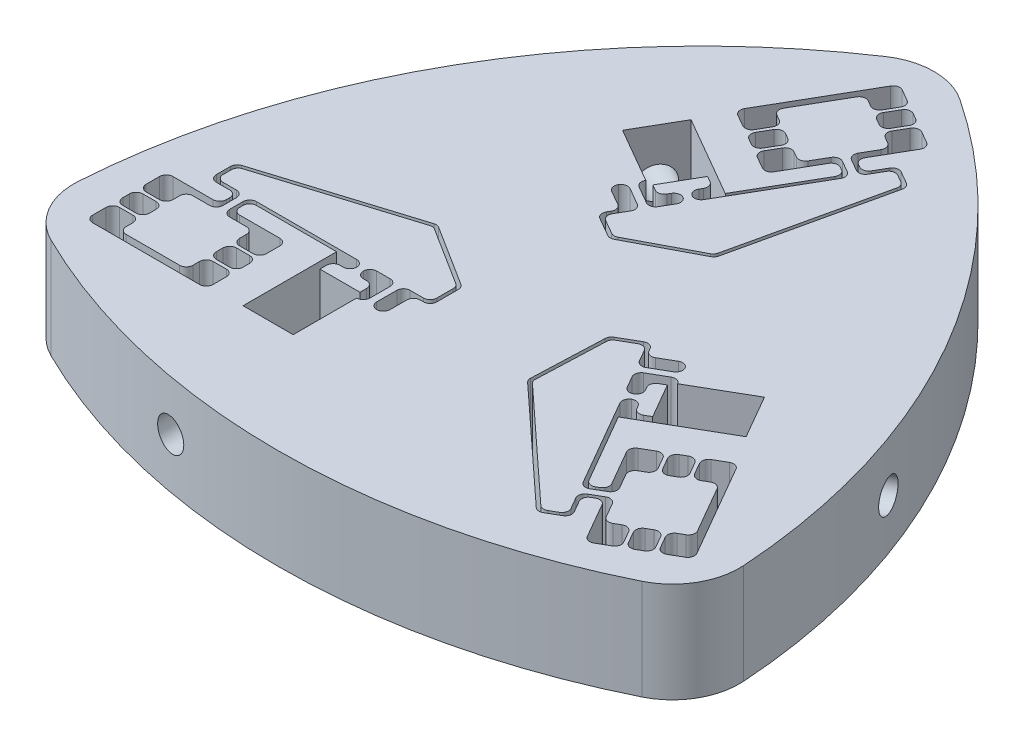
SolidWorks part; units mm, degrees
material "7050-T73510"
ref_plane "Front Plane" through (0, 0, 0) normal (0, 0, 1) x (1, 0, 0)
ref_plane "Top Plane" through (0, 0, 0) normal (0, 1, 0) x (1, 0, 0)
ref_plane "Right Plane" through (0, 0, 0) normal (1, 0, 0) x (0, 0, -1)
sketch "Bass" plane through (0, 0, 0) normal (0, 1, 0) x (1, 0, 0)
  line L1 (0, 57.735) -> (-50, -28.8675) construction
  line L2 (-50, -28.8675) -> (50, -28.8675) construction
  line L3 (50, -28.8675) -> (0, 57.735) construction
  circle A0 centre (0, 0) radius 28.8675 construction
  arc A1 (0, 57.735) -> (50, -28.8675) centre (-50, -28.8675) cw
  arc A2 (-50, -28.8675) -> (0, 57.735) centre (50, -28.8675) cw
  arc A3 (-50, -28.8675) -> (50, -28.8675) centre (0, 57.735) ccw
  dimension "D1" = 100
extrude "Drop the" add sketch "Bass" against normal blind 15
sketch "Flexin" plane through (0, 0, 0) normal (0, -1, 0) x (1, 0, 0)
  line L0 (-8.4558, -18.5533) -> (-7.9558, -19.4193)
  line L1 (-7.9558, -19.4193) -> (-3.6256, -16.9193)
  line L2 (-3.6256, -16.9193) -> (-1.6256, -20.3834)
  line L5 (-1.6256, -20.3834) -> (-3.3577, -21.3834)
  line L6 (-3.3577, -21.3834) -> (-4.6077, -19.2184)
  line L7 (-4.6077, -19.2184) -> (-6.3397, -20.2184)
  line L8 (-6.3397, -20.2184) -> (-3.3397, -25.4145)
  line L9 (-3.3397, -25.4145) -> (-1.6077, -24.4145)
  line L10 (-1.6077, -24.4145) -> (-2.8577, -22.2495)
  line L11 (-2.8577, -22.2495) -> (-1.1256, -21.2495)
  line L14 (-1.1256, -21.2495) -> (7.3744, -35.9719)
  line L15 (7.3744, -35.9719) -> (3.9103, -37.9719)
  line L16 (3.9103, -37.9719) -> (1.6603, -34.0748)
  line L17 (1.6603, -34.0748) -> (-0.9378, -35.5748)
  line L18 (-0.9378, -35.5748) -> (-2.9378, -32.1107)
  line L19 (-2.9378, -32.1107) -> (-3.3708, -32.3607)
  line L20 (-3.3708, -32.3607) -> (-1.3708, -35.8248)
  line L21 (-1.3708, -35.8248) -> (-3.9689, -37.3248)
  line L22 (-3.9689, -37.3248) -> (-5.9689, -33.8607)
  line L23 (-5.9689, -33.8607) -> (-6.4019, -34.1107)
  line L24 (-6.4019, -34.1107) -> (-4.4019, -37.5748)
  line L25 (-4.4019, -37.5748) -> (-7, -39.0748)
  line L26 (-7, -39.0748) -> (-2, -47.735)
  line L27 (-2, -47.735) -> (0.5981, -46.235)
  line L28 (0.5981, -46.235) -> (2.5981, -49.6991)
  line L29 (2.5981, -49.6991) -> (3.0311, -49.4491)
  line L30 (3.0311, -49.4491) -> (1.0311, -45.985)
  line L31 (1.0311, -45.985) -> (3.6292, -44.485)
  line L32 (3.6292, -44.485) -> (5.6292, -47.9491)
  line L33 (5.6292, -47.9491) -> (6.0622, -47.6991)
  line L34 (6.0622, -47.6991) -> (4.0622, -44.235)
  line L35 (4.0622, -44.235) -> (6.6603, -42.735)
  line L36 (6.6603, -42.735) -> (4.4103, -38.8379)
  line L37 (4.4103, -38.8379) -> (7.8744, -36.8379)
  line L38 (7.8744, -36.8379) -> (9.8744, -40.302)
  line L39 (9.8744, -40.302) -> (12.4724, -38.802)
  line L40 (12.4724, -38.802) -> (7.2846, -15.8164)
  line L41 (7.2846, -15.8164) -> (-2.6615, -10.5892)
  line L42 (-2.6615, -10.5892) -> (-6.1256, -12.5892)
  line L43 (-6.1256, -12.5892) -> (-4.1256, -16.0533)
  line L44 (-4.1256, -16.0533) -> (-8.4558, -18.5533)
  line L45 (-8.2058, -18.9863) -> (-3.8756, -16.4863) construction
  line L46 (-4.8397, -22.8164) -> (-1.3756, -20.8164) construction
  line L47 (-4.5, -43.4049) -> (7.6244, -36.4049) construction
  line L48 (-15.683, -25.0354) -> (-7.4558, -20.2854)
  line L49 (-7.4558, -20.2854) -> (-7.9558, -19.4193)
  line L50 (-9.866, -36.1107) -> (-0.866, -51.6991)
  line L51 (-0.866, -51.6991) -> (2.5981, -49.6991)
  line L52 (3.0311, -49.4491) -> (5.6292, -47.9491)
  line L53 (-15.683, -25.0354) -> (-11.933, -31.5305)
  line L54 (-11.933, -31.5305) -> (0.1913, -24.5305)
  line L55 (6.0622, -47.6991) -> (9.5263, -45.6991)
  line L56 (-9.866, -36.1107) -> (-6.4019, -34.1107)
  line L57 (0.1913, -24.5305) -> (6.6913, -35.7889)
  line L58 (6.6913, -35.7889) -> (4.5263, -37.0389)
  line L59 (4.5263, -37.0389) -> (0.5263, -30.1107)
  line L64 (-5.9689, -33.8607) -> (-3.3708, -32.3607)
  line L65 (-2.9378, -32.1107) -> (0.5263, -30.1107)
  line L66 (9.5263, -45.6991) -> (5.5263, -38.7709)
  line L78 (5.5263, -38.7709) -> (7.6913, -37.5209)
  line L79 (7.6913, -37.5209) -> (9.6913, -40.985)
  line L80 (9.6913, -40.985) -> (13.0412, -39.051)
  line L81 (13.0412, -39.051) -> (7.7215, -15.4812)
  line L82 (7.7215, -15.4812) -> (-2.6729, -10.0184)
  line L83 (-2.6729, -10.0184) -> (-6.8087, -12.4062)
  line L84 (-6.8087, -12.4062) -> (-5.5587, -14.5713)
  line L85 (-5.5587, -14.5713) -> (-9.4558, -16.8213)
  line L88 (-8.4558, -18.5533) -> (-9.4558, -16.8213)
  point P87 (-1.9917, -21.7495)
  dimension "D1" = 4
  dimension "D2" = 1
  dimension "D3" = 4
  dimension "D4" = 1
  dimension "D5" = 5
  dimension "D6" = 1
  dimension "D7" = 10
  dimension "D8" = 10
  dimension "D9" = 17
  dimension "D10" = 18
  dimension "D11" = 0.5
  dimension "D12" = 3
  dimension "D13" = 3
  dimension "D14" = 4
  dimension "D15" = 2
  dimension "D16" = 6
  dimension "D17" = 4
  dimension "D18" = 4
  dimension "D19" = 4
  dimension "D20" = 10
  dimension "D21" = 32
  dimension "D22" = 4
  dimension "D23" = 3
  dimension "D24" = 5
  dimension "D25" = 0.5
  dimension "D26" = 0.5
  dimension "D27" = 0.5
  dimension "D28" = 0.5
  dimension "D29" = 0.5
  dimension "D30" = 0.5
  dimension "D31" = 1
  dimension "D32" = 1
  dimension "D34" = 1
  dimension "D35" = 1
  dimension "D36" = 2
  dimension "D38" = 10.5
  dimension "D46" = 10
  dimension "D47" = 2
extrude "Now we" cut sketch "Flexin" along normal through all contours L24 L25 L26 L27 L28 | L30 L31 L32 | L44 L88 L85 L84 L83 L82 L81 L80 L79 L78 L34 L35 L36 L37 L38 L39 L40 L41 L42 L43 | L59 L58 L57 L54 L53 L48 L49 L1 L2 L5 L6 L7 L8 L9 L10 L11 L14 L15 L16 L17 L18 | L20 L21 L22 region at (-8.5757, 0, -17.4678) region at (-5.8515, 0, -26.5152) region at (-3.6699, 0, -34.8427) region at (-5.5886, 0, -35.9505) region at (3.3301, 0, -46.9671)
hole_wizard "3/16 (0.1875) Diameter Hole1" positions "Sketch4" profile "Sketch3" hole size "3/16" standard "ANSI Inch" end condition up to next
sketch "Sketch4" plane through (-22.6029, 0, -13.0498) normal (0.866, 0, 0.5) x (0.5, 0, -0.866)
  line L0 (13.8397, 0) -> (21.3397, 0) construction
  line L1 (21.3397, -15) -> (21.3397, 0) construction
  point P0 (17.5897, -7.5)
  dimension "D1" = 7.5
  dimension "D2" = 3.75
sketch "Sketch3" plane through (-13.808, -7.5, -28.2829) normal (0, 1, 0) x (0.5, 0, -0.866)
  line L0 (0, 0) -> (0, 44.158)
  line L1 (0, 44.158) -> (2.3812, 44.158)
  line L2 (2.3812, 44.158) -> (2.3812, 0)
  line L5 (2.3812, 0) -> (0, 0)
  line L11 (0, -6.35) -> (0, 107.95) construction
  dimension "Thru Hole Dia." = 4.7625
  dimension "Thru Hole Depth" = 44.158
fillet "Flexy Fish" radius 1 54 edges at (4.4103, -7.5, -38.8379) (7.8744, -7.5, -36.8379) (7.6913, -7.5, -37.5209) (7.3744, -7.5, -35.9719) (6.6913, -7.5, -35.7889) (4.5263, -7.5, -37.0389) (3.9103, -7.5, -37.9719) (-2.6729, -7.5, -10.0184) (-2.6615, -7.5, -10.5892) (7.2846, -7.5, -15.8164) (7.7215, -7.5, -15.4812) (12.4724, -7.5, -38.802) (13.0412, -7.5, -39.051) (9.6913, -7.5, -40.985) (9.8744, -7.5, -40.302) (-7.9558, -7.5, -19.4193) (-8.4558, -7.5, -18.5533) (-4.1256, -7.5, -16.0533) (-5.5587, -7.5, -14.5713) (-6.1256, -7.5, -12.5892) (-6.8087, -7.5, -12.4062) (-2.8577, -7.5, -22.2495) (-1.1256, -7.5, -21.2495) (-1.6256, -7.5, -20.3834) (-3.3577, -7.5, -21.3834) (-3.6256, -7.5, -16.9193) (3.6292, -7.5, -44.485) (4.0622, -7.5, -44.235) (6.6603, -7.5, -42.735) (-2, -7.5, -47.735) (1.0311, -7.5, -45.985) (1.6603, -7.5, -34.0748) (-0.9378, -7.5, -35.5748) (-1.3708, -7.5, -35.8248) (-3.9689, -7.5, -37.3248) (-4.4019, -7.5, -37.5748) (-7, -7.5, -39.0748) (0.5981, -7.5, -46.235) (-4.6077, -7.5, -19.2184) (-1.6077, -7.5, -24.4145) (-9.866, -7.5, -36.1107) (-6.4019, -7.5, -34.1107) (-5.9689, -7.5, -33.8607) (-3.3708, -7.5, -32.3607) (-2.9378, -7.5, -32.1107) (0.5263, -7.5, -30.1107) (5.5263, -7.5, -38.7709) (9.5263, -7.5, -45.6991) (6.0622, -7.5, -47.6991) (5.6292, -7.5, -47.9491) (2.5981, -7.5, -49.6991) (3.0311, -7.5, -49.4491) (-0.866, -7.5, -51.6991) (-9.4558, -7.5, -16.8213)
fillet "Fillet o' Bass" radius 10 3 edges at (50, -7.5, 28.8675) (-50, -7.5, 28.8675) (0, -7.5, -57.735)
sketch "Reference Top Plane" plane through (0, 0, 0) normal (0, 1, 0) x (1, 0, 0)
  line L0 (-1000, 0) -> (49000, 0) construction
  line L1 (0, -1000) -> (0, 49000) construction
sketch "Reference Y-Axis" plane through (0, 0, 0) normal (1, 0, 0) x (0, 0, -1)
  line L0 (0, -1000) -> (0, 49000) construction
pattern_circular "Reflexurn" count 3 over 360 about axis through (0, -1000, 0) along (0, 1, 0) of "Now we", "Flexy Fish", "3/16 (0.1875) Diameter Hole1"
equation "\"offsetDistance\"=0.5"
